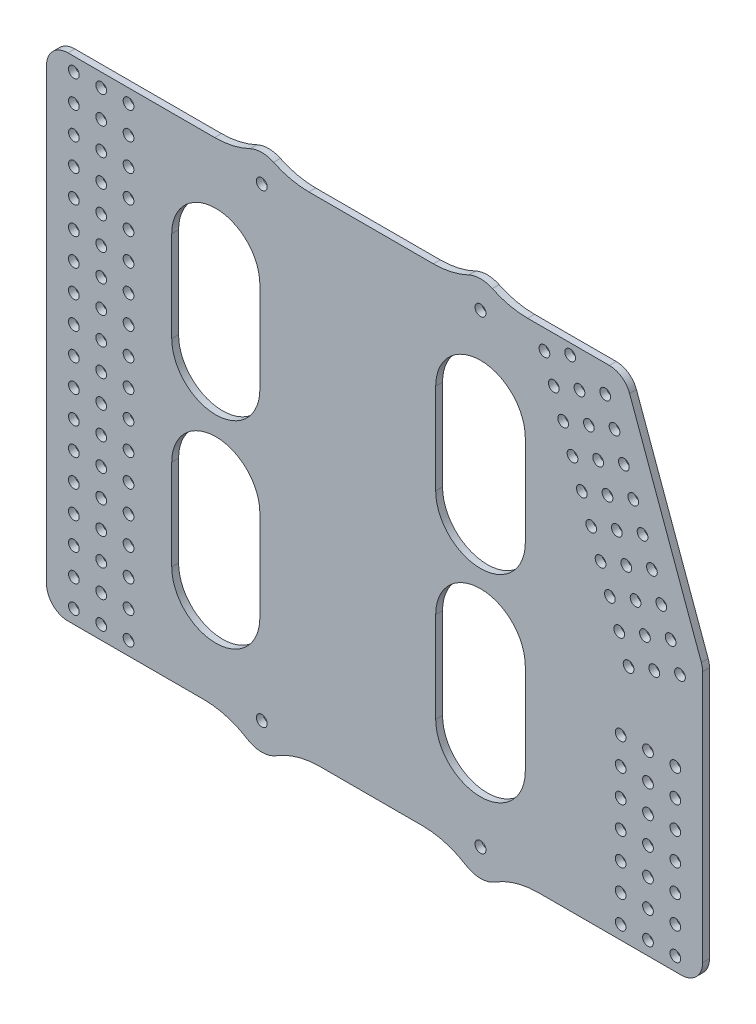
SolidWorks part; units mm, degrees
ref_plane "Front Plane" through (0, 0, 0) normal (0, 0, 1) x (1, 0, 0)
ref_plane "Top Plane" through (0, 0, 0) normal (0, 1, 0) x (1, 0, 0)
ref_plane "Right Plane" through (0, 0, 0) normal (1, 0, 0) x (0, 0, -1)
sketch "Sketch3" plane through (0, 0, 0) normal (0, 0, 1) x (1, 0, 0)
  line L0 (-62.0347, 275.0603) -> (206.4353, 275.0603)
  line L1 (204.6653, 90.9103) -> (204.6653, 78.2103) construction
  line L3 (206.4353, 275.0603) -> (242.7653, 175.2445)
  line L4 (242.7653, 175.2445) -> (242.7653, 46.4603)
  line L6 (242.7653, 46.4603) -> (-62.0347, 46.4603)
  line L7 (-62.0347, 46.4603) -> (-62.0347, 275.0603)
  line L8 (-49.3347, 268.7103) -> (-36.6347, 268.7103) construction
  line L9 (-49.3347, 268.7103) -> (-49.3347, 256.0103) construction
  line L10 (105.1393, -854.8604) -> (105.1393, 49145.1396) construction
  line L11 (169.2687, 265.7779) -> (173.6123, 253.8438) construction
  line L12 (204.6653, 129.0103) -> (204.6653, 116.3103) construction
  line L13 (23.6016, 116.2566) -> (23.6016, 141.6566) construction
  line L14 (23.6016, 185.8526) -> (23.6016, 211.2526) construction
  line L15 (-894.8607, 145.1396) -> (49105.1393, 145.1396) construction
  circle A0 centre (123.2241, 114.6088) radius 2.4892
  circle A1 centre (87.0545, 114.6088) radius 2.4892
  circle A2 centre (-49.3347, 268.7103) radius 2.4892
  circle A3 centre (-49.3347, 90.9103) radius 2.4892
  circle A4 centre (-36.6347, 268.7103) radius 2.4892
  circle A5 centre (-23.9347, 268.7103) radius 2.4892
  circle A6 centre (-36.6347, 256.0103) radius 2.4892
  circle A7 centre (-23.9347, 256.0103) radius 2.4892
  circle A8 centre (-36.6347, 243.3103) radius 2.4892
  circle A9 centre (-23.9347, 243.3103) radius 2.4892
  circle A10 centre (-36.6347, 230.6103) radius 2.4892
  circle A11 centre (-23.9347, 230.6103) radius 2.4892
  circle A12 centre (-36.6347, 217.9103) radius 2.4892
  circle A13 centre (-23.9347, 217.9103) radius 2.4892
  circle A14 centre (-36.6347, 205.2103) radius 2.4892
  circle A15 centre (-23.9347, 205.2103) radius 2.4892
  circle A16 centre (-36.6347, 192.5103) radius 2.4892
  circle A17 centre (-23.9347, 192.5103) radius 2.4892
  circle A18 centre (-36.6347, 179.8103) radius 2.4892
  circle A19 centre (-23.9347, 179.8103) radius 2.4892
  circle A20 centre (-36.6347, 167.1103) radius 2.4892
  circle A21 centre (-23.9347, 167.1103) radius 2.4892
  circle A22 centre (-36.6347, 154.4103) radius 2.4892
  circle A23 centre (-23.9347, 154.4103) radius 2.4892
  circle A24 centre (-36.6347, 141.7103) radius 2.4892
  circle A25 centre (-23.9347, 141.7103) radius 2.4892
  circle A26 centre (-36.6347, 129.0103) radius 2.4892
  circle A27 centre (-23.9347, 129.0103) radius 2.4892
  circle A28 centre (-36.6347, 116.3103) radius 2.4892
  circle A29 centre (-23.9347, 116.3103) radius 2.4892
  circle A30 centre (-36.6347, 103.6103) radius 2.4892
  circle A31 centre (-23.9347, 103.6103) radius 2.4892
  circle A32 centre (-36.6347, 90.9103) radius 2.4892
  circle A33 centre (-23.9347, 90.9103) radius 2.4892
  circle A34 centre (-49.3347, 256.0103) radius 2.4892
  circle A35 centre (-49.3347, 243.3103) radius 2.4892
  circle A36 centre (-49.3347, 230.6103) radius 2.4892
  circle A37 centre (-49.3347, 217.9103) radius 2.4892
  circle A38 centre (-49.3347, 205.2103) radius 2.4892
  circle A39 centre (-49.3347, 192.5103) radius 2.4892
  circle A40 centre (-49.3347, 179.8103) radius 2.4892
  circle A41 centre (-49.3347, 167.1103) radius 2.4892
  circle A42 centre (-49.3347, 154.4103) radius 2.4892
  circle A43 centre (-49.3347, 141.7103) radius 2.4892
  circle A44 centre (-49.3347, 129.0103) radius 2.4892
  circle A45 centre (-49.3347, 116.3103) radius 2.4892
  circle A46 centre (-49.3347, 103.6103) radius 2.4892
  circle A47 centre (-49.3347, 90.9103) radius 2.4892
  circle A48 centre (169.2687, 265.7779) radius 2.4892
  circle A49 centre (181.2028, 270.1215) radius 2.4892
  circle A50 centre (197.4805, 262.5311) radius 2.4892
  circle A51 centre (173.6123, 253.8438) radius 2.4892
  circle A52 centre (185.5464, 258.1874) radius 2.4892
  circle A53 centre (201.8242, 250.597) radius 2.4892
  circle A54 centre (177.956, 241.9097) radius 2.4892
  circle A55 centre (189.8901, 246.2533) radius 2.4892
  circle A56 centre (206.1678, 238.6629) radius 2.4892
  circle A57 centre (182.2996, 229.9756) radius 2.4892
  circle A58 centre (194.2337, 234.3192) radius 2.4892
  circle A59 centre (210.5115, 226.7288) radius 2.4892
  circle A60 centre (186.6433, 218.0415) radius 2.4892
  circle A61 centre (198.5774, 222.3851) radius 2.4892
  circle A62 centre (214.8551, 214.7947) radius 2.4892
  circle A63 centre (190.9869, 206.1074) radius 2.4892
  circle A64 centre (202.921, 210.451) radius 2.4892
  circle A65 centre (219.1988, 202.8606) radius 2.4892
  circle A66 centre (195.3306, 194.1733) radius 2.4892
  circle A67 centre (207.2647, 198.5169) radius 2.4892
  circle A68 centre (223.5424, 190.9265) radius 2.4892
  circle A69 centre (199.6743, 182.2392) radius 2.4892
  circle A70 centre (211.6083, 186.5828) radius 2.4892
  circle A71 centre (227.8861, 178.9924) radius 2.4892
  circle A72 centre (204.0179, 170.3051) radius 2.4892
  circle A73 centre (215.952, 174.6488) radius 2.4892
  circle A74 centre (232.2298, 167.0583) radius 2.4892
  circle A75 centre (208.3616, 158.371) radius 2.4892
  circle A76 centre (220.2957, 162.7147) radius 2.4892
  circle A78 centre (236.5734, 155.1242) radius 2.4892 [skipped]
  circle A79 centre (204.6653, 129.0103) radius 2.4892
  circle A80 centre (217.3653, 129.0103) radius 2.4892
  circle A81 centre (230.0653, 129.0103) radius 2.4892
  circle A82 centre (204.6653, 116.3103) radius 2.4892
  circle A83 centre (217.3653, 116.3103) radius 2.4892
  circle A84 centre (230.0653, 116.3103) radius 2.4892
  circle A85 centre (204.6653, 103.6103) radius 2.4892
  circle A86 centre (217.3653, 103.6103) radius 2.4892
  circle A87 centre (230.0653, 103.6103) radius 2.4892
  circle A88 centre (204.6653, 90.9103) radius 2.4892
  circle A89 centre (217.3653, 90.9103) radius 2.4892
  circle A90 centre (230.0653, 90.9103) radius 2.4892
  circle A91 centre (23.6016, 185.8526) radius 14.2875
  circle A92 centre (52.1422, 151.0564) radius 14.2875
  circle A93 centre (23.6016, 116.2566) radius 14.2875
  circle A94 centre (105.1393, 145.1396) radius 14.2875
  circle A95 centre (104.9447, 224.8273) radius 14.2875
  circle A96 centre (144.1424, 181.3926) radius 14.2875
  circle A99 centre (85.284, 241.0108) radius 2.4892
  circle A100 centre (23.6016, 141.6566) radius 2.4892
  circle A101 centre (45.5987, 128.9566) radius 2.4892
  circle A102 centre (45.5987, 103.5566) radius 2.4892
  circle A103 centre (23.6016, 90.8566) radius 2.4892
  circle A104 centre (1.6046, 103.5566) radius 2.4892
  circle A105 centre (1.6046, 128.9566) radius 2.4892
  circle A106 centre (23.6016, 211.2526) radius 2.4892
  circle A107 centre (45.5987, 198.5526) radius 2.4892
  circle A108 centre (45.5987, 173.1526) radius 2.4892
  circle A109 centre (23.6016, 160.4526) radius 2.4892
  circle A110 centre (1.6046, 173.1526) radius 2.4892
  circle A111 centre (1.6046, 198.5526) radius 2.4892
  circle A112 centre (123.2241, 175.6704) radius 2.4892
  circle A113 centre (87.0545, 175.6704) radius 2.4892
  circle A116 centre (124.6065, 208.849) radius 2.4892
  circle A117 centre (-49.3347, 78.2103) radius 2.4892
  circle A118 centre (-36.6347, 78.2103) radius 2.4892
  circle A119 centre (-23.9347, 78.2103) radius 2.4892
  circle A120 centre (-49.3347, 65.5103) radius 2.4892
  circle A121 centre (-36.6347, 65.5103) radius 2.4892
  circle A122 centre (-23.9347, 65.5103) radius 2.4892
  circle A123 centre (-49.3347, 52.8103) radius 2.4892
  circle A124 centre (-36.6347, 52.8103) radius 2.4892
  circle A125 centre (-23.9347, 52.8103) radius 2.4892
  circle A126 centre (204.6653, 78.2103) radius 2.4892
  circle A127 centre (217.3653, 78.2103) radius 2.4892
  circle A128 centre (230.0653, 78.2103) radius 2.4892
  circle A129 centre (204.6653, 65.5103) radius 2.4892
  circle A130 centre (217.3653, 65.5103) radius 2.4892
  circle A131 centre (230.0653, 65.5103) radius 2.4892
  circle A132 centre (204.6653, 52.8103) radius 2.4892
  circle A133 centre (217.3653, 52.8103) radius 2.4892
  circle A134 centre (230.0653, 52.8103) radius 2.4892
  dimension "D1" = 4.9784
  dimension "D2" = 6.35
  dimension "D10" = 4.9784
  dimension "D11" = 4.9784
  dimension "D12" = 4.9784
  dimension "D15" = 4.9784
  dimension "D16" = 4.9784
  dimension "D17" = 4.9784
  dimension "D20" = 4.9784
  dimension "D21" = 28.575
  dimension "D22" = 28.575
  dimension "D23" = 28.575
  dimension "D24" = 28.575
  dimension "D25" = 28.575
  dimension "D26" = 28.575
  dimension "D27" = 12.7
  dimension "D28" = 4.9784
  dimension "D32" = 4.9784
  dimension "D35" = 4.9784
  dimension "D38" = 4.9784
  dimension "D5" = 3
  dimension "D7" = 12.7
  dimension "D8" = 12.7
  dimension "D9" = 228.6
  dimension "D14" = 12.7
  dimension "D19" = 12.7
  dimension "D29" = 25.4
  dimension "D31" = 25.4
  dimension "D33" = 6
  dimension "D34" = 25.4
  dimension "D36" = 18.0848
  dimension "D37" = 30.5308
  dimension "D39" = 19.6607
  dimension "D40" = 16.1835
  dimension "D41" = 12.7
  dimension "D42" = 15.9782
  dimension "D43" = 19.6618
  dimension "D6" = 15
  dimension "D13" = 10
  dimension "D18" = 4
  dimension "D30" = 6
extrude "Boss-Extrude3" add sketch "Sketch3" along normal blind 3.175
fillet "Fillet2" radius 10 5 edges at (-62.0347, 275.0603, 1.5875) (-62.0347, 46.4603, 1.5875) (242.7653, 46.4603, 1.5875) (242.7653, 175.2445, 1.5875) (206.4353, 275.0603, 1.5875)
sketch "Sketch5" plane through (0, 0, 3.175) normal (0, 0, 1) x (1, 0, 0)
  circle A0 centre (23.6016, 185.8526) radius 14.2875
  circle A1 centre (23.6016, 211.2526) radius 2.4892
  circle A2 centre (45.5987, 198.5526) radius 2.4892
  circle A3 centre (1.6046, 198.5526) radius 2.4892
  circle A4 centre (1.6046, 173.1526) radius 2.4892
  circle A5 centre (23.6016, 160.4526) radius 2.4892
  circle A6 centre (45.5987, 173.1526) radius 2.4892
  circle A7 centre (23.6016, 116.2566) radius 14.2875
  circle A8 centre (1.6046, 128.9566) radius 2.4892
  circle A9 centre (23.6016, 141.6566) radius 2.4892
  circle A10 centre (45.5987, 128.9566) radius 2.4892
  circle A11 centre (1.6046, 103.5566) radius 2.4892
  circle A12 centre (23.6016, 90.8566) radius 2.4892
  circle A13 centre (45.5987, 103.5566) radius 2.4892
  circle A14 centre (52.1422, 151.0564) radius 14.2875
  circle A15 centre (105.1393, 145.1396) radius 14.2875
  circle A16 centre (87.0545, 114.6088) radius 2.4892
  circle A17 centre (123.2241, 114.6088) radius 2.4892
  circle A18 centre (87.0545, 175.6704) radius 2.4892
  circle A19 centre (123.2241, 175.6704) radius 2.4892
  circle A20 centre (144.1424, 181.3926) radius 14.2875
  circle A21 centre (104.9447, 224.8273) radius 14.2875
  circle A22 centre (124.6065, 208.849) radius 2.4892
  circle A23 centre (85.284, 241.0108) radius 2.4892
extrude "Boss-Extrude5" add sketch "Sketch5" against normal blind 3.175
sketch "Sketch6" plane through (0, 0, 3.175) normal (0, 0, 1) x (1, 0, 0)
  line L0 (16.6029, 184.2341) -> (16.6029, 226.3723) construction
  line L3 (-3.8642, 184.2341) -> (-3.8642, 226.3723)
  line L4 (32.254, 159.3691) -> (143.252, 159.3691) construction
  line L5 (87.753, 159.3691) -> (87.753, 108.5741) construction
  line L6 (37.0701, 184.2341) -> (37.0701, 226.3723)
  line L9 (-62.0347, 265.0603) -> (-62.0347, 56.4603) construction
  line L10 (87.753, 268.0089) -> (87.753, 52.1089) construction
  line L11 (87.753, 159.3691) -> (276.8248, 159.3691) construction
  line L12 (139.5653, 184.2341) -> (139.5653, 226.3723) construction
  line L13 (118.7562, 184.2341) -> (118.7562, 226.3723)
  line L14 (160.3743, 184.2341) -> (160.3743, 226.3723)
  line L15 (139.5653, 134.504) -> (139.5653, 92.3658) construction
  line L16 (118.7562, 134.504) -> (118.7562, 92.3658)
  line L17 (160.3743, 134.504) -> (160.3743, 92.3658)
  line L18 (16.6029, 134.504) -> (16.6029, 92.3658) construction
  line L19 (-3.8642, 134.504) -> (-3.8642, 92.3658)
  line L20 (37.0701, 134.504) -> (37.0701, 92.3658)
  circle A4 centre (37.9653, 267.3191) radius 2.54
  circle A5 centre (139.5653, 267.3191) radius 2.54
  circle A6 centre (139.5653, 51.4191) radius 2.54
  circle A7 centre (37.9653, 51.4191) radius 2.54
  arc A8 (-3.8642, 184.2341) -> (37.0701, 184.2341) centre (16.6029, 184.2341) ccw
  arc A9 (37.0701, 226.3723) -> (-3.8642, 226.3723) centre (16.6029, 226.3723) ccw
  arc A10 (118.7562, 184.2341) -> (160.3743, 184.2341) centre (139.5653, 184.2341) ccw
  arc A11 (160.3743, 226.3723) -> (118.7562, 226.3723) centre (139.5653, 226.3723) ccw
  arc A12 (118.7562, 134.504) -> (160.3743, 134.504) centre (139.5653, 134.504) cw
  arc A13 (160.3743, 92.3658) -> (118.7562, 92.3658) centre (139.5653, 92.3658) cw
  arc A14 (-3.8642, 134.504) -> (37.0701, 134.504) centre (16.6029, 134.504) cw
  arc A15 (37.0701, 92.3658) -> (-3.8642, 92.3658) centre (16.6029, 92.3658) cw
  point P2 (16.6029, 205.3032)
  point P9 (139.5653, 205.3032)
  point P20 (139.5653, 113.4349)
  point P40 (16.6029, 113.4349)
  dimension "D4" = 5.08
  dimension "D5" = 5.08
  dimension "D3" = 110.998
  dimension "D6" = 101.6
  dimension "D7" = 100
  dimension "D8" = 215.9
  dimension "D9" = 215.9
extrude "Cut-Extrude1" cut sketch "Sketch6" against normal blind 3.175
sketch "Sketch7" plane through (0, 0, 3.175) normal (0, 0, 1) x (1, 0, 0)
  line L0 (-52.0347, 46.4603) -> (232.7653, 46.4603) construction
  line L1 (199.4332, 275.0603) -> (-52.0347, 275.0603) construction
  line L2 (16.0742, 275.0603) -> (59.8564, 275.0603)
  line L3 (117.6742, 275.0603) -> (161.4564, 275.0603)
  line L4 (112.6101, 46.4603) -> (166.5205, 46.4603)
  line L5 (11.0101, 46.4603) -> (64.9205, 46.4603)
  arc A0 (31.2265, 40.6544) -> (44.7041, 40.6544) centre (37.9653, 51.4191) ccw
  arc A1 (11.0101, 46.4603) -> (31.2265, 40.6544) centre (11.0101, 8.3603) cw
  arc A2 (44.7041, 40.6544) -> (64.9205, 46.4603) centre (64.9205, 8.3603) cw
  arc A3 (132.8265, 40.6544) -> (146.3041, 40.6544) centre (139.5653, 51.4191) ccw
  arc A4 (112.6101, 46.4603) -> (132.8265, 40.6544) centre (112.6101, 8.3603) cw
  arc A5 (146.3041, 40.6544) -> (166.5205, 46.4603) centre (166.5205, 8.3603) cw
  arc A6 (129.4973, 275.0603) -> (149.6332, 275.0603) centre (139.5653, 267.3191) ccw
  arc A7 (117.6742, 275.0603) -> (134.0925, 278.7794) centre (117.6742, 313.1603) ccw
  arc A8 (145.038, 278.7794) -> (161.4564, 275.0603) centre (161.4564, 313.1603) ccw
  arc A10 (27.8973, 275.0603) -> (48.0332, 275.0603) centre (37.9653, 267.3191) ccw
  arc A11 (43.438, 278.7794) -> (59.8564, 275.0603) centre (59.8564, 313.1603) ccw
  arc A12 (16.0742, 275.0603) -> (32.4925, 278.7794) centre (16.0742, 313.1603) ccw
  arc A13 (49.6572, 46.4603) -> (26.2734, 46.4603) centre (37.9653, 51.4191) ccw
  arc A14 (151.2572, 46.4603) -> (127.8734, 46.4603) centre (139.5653, 51.4191) ccw
  arc A15 (43.438, 278.7794) -> (32.4925, 278.7794) centre (37.9653, 267.3191) ccw
  arc A16 (145.038, 278.7794) -> (134.0925, 278.7794) centre (139.5653, 267.3191) ccw
  dimension "D1" = 25.4
  dimension "D2" = 38.1
  dimension "D3" = 38.1
  dimension "D4" = 25.4
  dimension "D5" = 38.1
  dimension "D6" = 25.4
  dimension "D7" = 38.1
extrude "Boss-Extrude6" add sketch "Sketch7" against normal up to surface (3.175 mm away) contours A11 A15 A12 L2 | A8 A16 A7 L3 | A0 A2 L5 A1 | A3 A5 L4 A4 region at (37.9653, 276.8249, 3.175) region at (139.5653, 276.8249, 3.175) region at (139.5653, 43.7015, 3.175) region at (37.9653, 43.7015, 3.175) up to face at (137.0253, 51.4191, 0)
